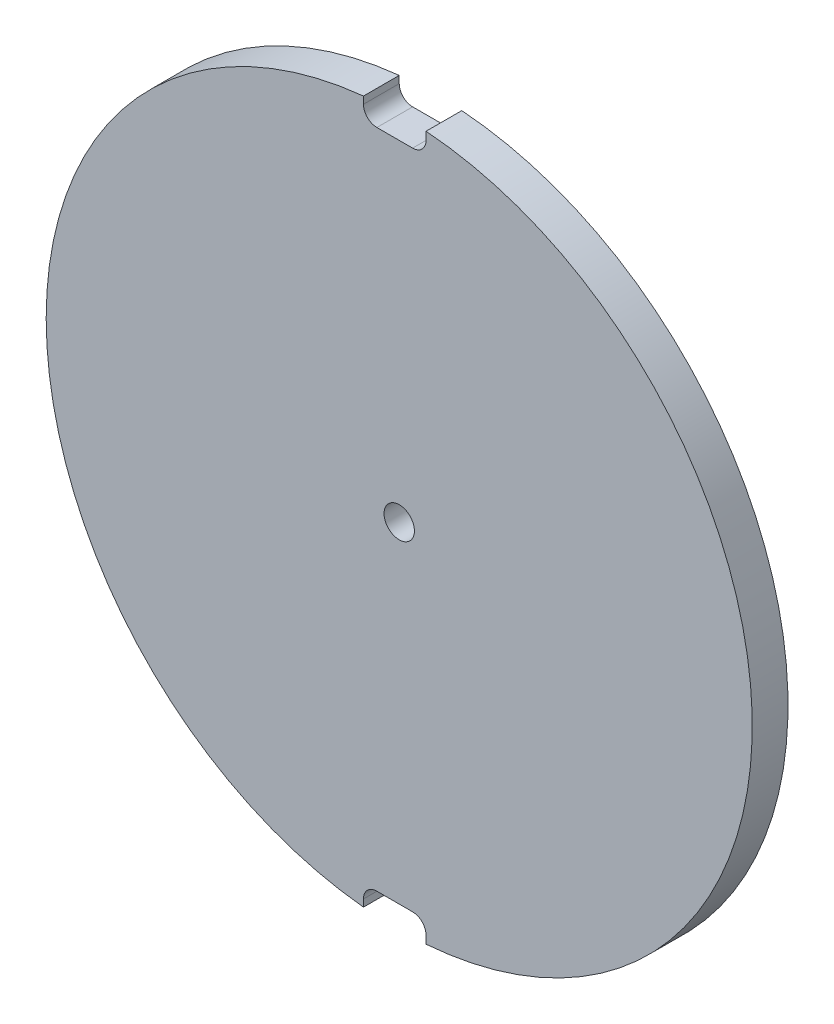
SolidWorks part; units mm, degrees
ref_plane "Płaszczyzna przednia" through (0, 0, 0) normal (0, 0, 1) x (1, 0, 0)
ref_plane "Płaszczyzna górna" through (0, 0, 0) normal (0, 1, 0) x (1, 0, 0)
ref_plane "Płaszczyzna prawa" through (0, 0, 0) normal (1, 0, 0) x (0, 0, -1)
sketch "Sketch1" plane through (0, 0, 0) normal (0, 0, 1) x (1, 0, 0)
  circle A0 centre (-12.8255, 19.2383) radius 39.5
extrude "Boss-Extrude1" add sketch "Sketch1" along normal blind 4
sketch "Sketch3" plane through (0, 0, 4) normal (0, 0, 1) x (1, 0, 0)
  circle A0 centre (-12.8255, 19.2383) radius 35
sketch "Sketch6" plane through (0, 0, 4) normal (0, 0, 1) x (1, 0, 0)
  line L0 (-12.8255, 54.2383) -> (-12.8255, -15.7617)
  line L1 (-47.8255, 19.2383) -> (22.1745, 19.2383)
  circle A0 centre (-12.8255, 19.2383) radius 35 construction
sketch "Sketch5" plane through (0, 0, 4) normal (0, 0, 1) x (1, 0, 0)
  line L0 (-15.3255, 59.2383) -> (-11.3255, 59.2383)
  line L1 (-15.3255, -17.7617) -> (-11.3255, -17.7617)
  line L2 (-15.3255, -17.7617) -> (-15.3255, -20.7617)
  line L3 (-15.3255, -20.7617) -> (-11.3255, -20.7617)
  line L4 (-11.3255, -17.7617) -> (-11.3255, -20.7617)
  line L5 (-15.3255, 59.2383) -> (-15.3255, 56.2383)
  line L6 (-15.3255, 56.2383) -> (-11.3255, 56.2383)
  line L7 (-11.3255, 59.2383) -> (-11.3255, 56.2383)
  line L17 (-12.8255, 54.2383) -> (-12.8255, -15.7617) construction
  line L22 (-16.8255, -19.2617) -> (-16.8255, -24.0586)
  line L23 (-16.8255, -24.0586) -> (-9.8255, -24.0586)
  line L24 (-9.8255, -24.0586) -> (-9.8255, -19.2617)
  line L25 (-9.8255, -19.2617) -> (-16.8255, -19.2617)
  line L30 (-16.8255, 57.7383) -> (-16.8255, 62.1835)
  line L31 (-16.8255, 62.1835) -> (-9.8255, 62.1835)
  line L32 (-9.8255, 62.1835) -> (-9.8255, 57.7383)
  line L33 (-9.8255, 57.7383) -> (-16.8255, 57.7383)
  arc A0 (-11.3255, -17.7617) -> (-11.3255, -20.7617) centre (-11.3255, -19.2617) cw
  arc A1 (-15.3255, -17.7617) -> (-15.3255, -20.7617) centre (-15.3255, -19.2617) ccw
  arc A2 (-11.3255, 59.2383) -> (-11.3255, 56.2383) centre (-11.3255, 57.7383) cw
  arc A3 (-15.3255, 59.2383) -> (-15.3255, 56.2383) centre (-15.3255, 57.7383) ccw
  circle A8 centre (-12.8255, 19.2383) radius 39.5 construction
  dimension "D1" = 4
  dimension "D2" = 3
  dimension "D3" = 4
  dimension "D4" = 3
  dimension "D10" = 40
  dimension "D12" = 40
  dimension "D13" = 1.5
  dimension "D15" = 1.5
extrude "Cut-Extrude2" cut sketch "Sketch5" against normal blind 10 contours A2 L7 | L5 A3 | L2 A1 | L4 L1 L2 L3 | A0 L4 | L7 L33 L5 L6 | L33 L30 L31 L32 | L25 L22 L23 L24 region at (-13.3255, 56.9883, 4) region at (-15.9622, 57.1017, 4) region at (-10.6889, 57.1017, 4) region at (-13.3255, -18.5117, 4) region at (-15.9622, -18.6251, 4) region at (-10.6889, -18.6251, 4)
sketch "Sketch7" plane through (0, 0, 0) normal (0, 0, -1) x (-1, 0, 0)
  circle A0 centre (12.8255, 19.2383) radius 26
extrude "Boss-Extrude2" add sketch "Sketch7" along normal blind 7
sketch "Sketch8" plane through (0, 0, -7) normal (0, 0, -1) x (-1, 0, 0)
  circle A0 centre (12.8255, 19.2383) radius 1.7
extrude "Cut-Extrude3" cut sketch "Sketch8" against normal blind 20
sketch "Sketch9" plane through (0, 0, -7) normal (0, 0, -1) x (-1, 0, 0)
  circle A0 centre (12.8255, 19.2383) radius 5
extrude "Cut-Extrude4" cut sketch "Sketch9" against normal blind 4
